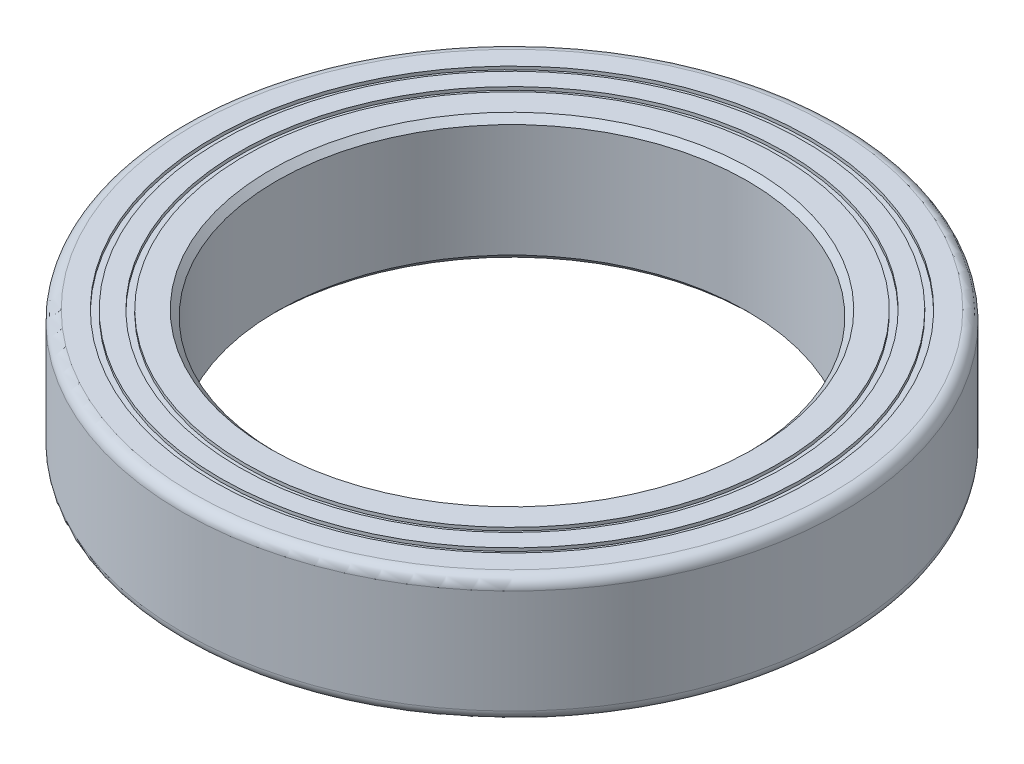
SolidWorks part; units mm, degrees
ref_plane "Front Plane" through (0, 0, 0) normal (0, 0, 1) x (1, 0, 0)
ref_plane "Top Plane" through (0, 0, 0) normal (0, 1, 0) x (1, 0, 0)
ref_plane "Right Plane" through (0, 0, 0) normal (1, 0, 0) x (0, 0, -1)
sketch "Sketch1" plane through (0, 0, 0) normal (0, 0, 1) x (1, 0, 0)
  line L0 (0, 0) -> (7.5, 0) construction
  line L1 (10.5, 0) -> (10.5, 4)
  line L3 (0, 2) -> (0, 0) construction
  line L4 (7.5, 0) -> (7.5, 4)
  line L5 (7.5, 0) -> (8.5, 0)
  line L6 (8.5, 0) -> (8.5, 0.1)
  line L7 (8.5, 0.1) -> (8.7, 0.1)
  line L8 (8.7, 0.1) -> (8.7, 0)
  line L9 (8.7, 0) -> (9.3, 0)
  line L10 (9, 0) -> (9, 2) construction
  line L11 (10.5, 2) -> (7.5, 2) construction
  line L12 (7.5, 2) -> (0, 2) construction
  line L13 (9.3, 0.1) -> (9.3, 0)
  line L14 (9.5, 0.1) -> (9.3, 0.1)
  line L15 (9.5, 0) -> (9.5, 0.1)
  line L16 (10.5, 0) -> (9.5, 0)
  line L17 (10.5, 4) -> (9.5, 4)
  line L18 (9.5, 4) -> (9.5, 3.9)
  line L19 (9.5, 3.9) -> (9.3, 3.9)
  line L20 (9.3, 3.9) -> (9.3, 4)
  line L21 (8.7, 4) -> (9.3, 4)
  line L22 (8.7, 3.9) -> (8.7, 4)
  line L23 (8.5, 3.9) -> (8.7, 3.9)
  line L24 (8.5, 4) -> (8.5, 3.9)
  line L25 (7.5, 4) -> (8.5, 4)
  dimension "D1" = 10.5
  dimension "D2" = 7.5
  dimension "D4" = 1
  dimension "D5" = 0.2
  dimension "D6" = 0.1
  dimension "D3" = 4
revolve "Revolve1" add sketch "Sketch1" angle 360 about L3
fillet "Fillet2" radius 0.344 2 edges at (0, 0, 10.5) (0, 4, 10.5)
chamfer "Chamfer2" distance 0.2 angle 45 2 edges at (0, 0, 7.5) (0, 4, 7.5)
equation "\"Ratio\"= 15"
equation "\"Hull Diameter\"= 3.5in"
equation "\"Fixed Ring Diameter\"= 76"
equation "\"Fixed Pin Diameter\"= 6"
equation "\"Output Ring Diameter\"= 40"
equation "\"Output Pin Diameter\"= 6"
equation "\"Disk Bearing Inner Diameter\"= 9"
equation "\"Disk Bearing Outer Diameter\"= 17"
equation "\"Disk Bearing Height\"= 5"
equation "\"Shaft Bearing Inner Diameter\"= 15"
equation "\"Shaft Bearing Outer Diameter\"= 21"
equation "\"Shaft Bearing Height\"= 4"
equation "\"Eccentricity\"= 1.5"
equation "\"Disk Height\"= 8"
equation "\"Disk Spacing\"= 5"
equation "\"Hull Height\"= 40"
equation "\"Shaft End Bearing Inner Diameter\"= 12"
equation "\"Shaft End Bearing Outer Diameter\"= 18"
equation "\"Shaft End Bearing Height\"= 4"
equation "\"Output Bearing Inner Diameter\"= 55"
equation "\"Output Bearing Outer Diameter\"= 72"
equation "\"Outer Bearing Height\"= 9"
equation "\"D3@Sketch1\"= \"Shaft Bearing Height\""
equation "\"D2@Sketch1\" = \"Shaft Bearing Inner Diameter\" / 2"
equation "\"D1@Sketch1\" = \"Shaft Bearing Outer Diameter\" / 2"
